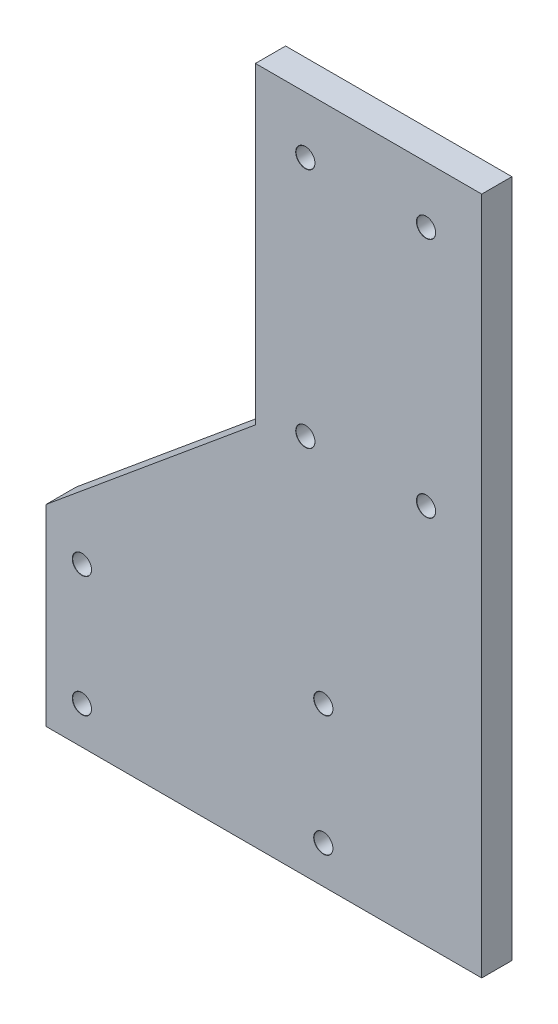
SolidWorks part; units mm, degrees
ref_plane "前视基准面" through (0, 0, 0) normal (0, 0, 1) x (1, 0, 0)
ref_plane "上视基准面" through (0, 0, 0) normal (0, 1, 0) x (1, 0, 0)
ref_plane "右视基准面" through (0, 0, 0) normal (1, 0, 0) x (0, 0, -1)
sketch "草图1" plane through (0, 0, 0) normal (0, 0, 1) x (1, 0, 0)
  line L0 (0, 0) -> (-41.5, 0)
  line L1 (-41.5, 0) -> (-41.5, 25.5)
  line L2 (-41.5, 25.5) -> (-13.75, 48.5)
  line L6 (14.05, -11.5) -> (-49.0563, -11.5) construction
  line L7 (-13.75, 48.5) -> (-13.75, 90)
  line L8 (-13.75, 90) -> (16.25, 90)
  line L9 (16.25, 90) -> (16.25, 0)
  line L10 (-92.1756, 35) -> (57.8057, 35) construction
  line L11 (-105.9645, 43.75) -> (59.2906, 43.75) construction
  line L12 (1.25, -9) -> (1.25, 87.7198) construction
  line L13 (0, 0) -> (16.25, 0)
  dimension "D1" = 41.5
  dimension "D2" = 90
  dimension "D3" = 25.5
  dimension "D4" = 30
  dimension "D5" = 41.5
  dimension "D6" = 35
  dimension "D7" = 8.75
extrude "凸台-拉伸1" add sketch "草图1" along normal blind 4
hole_wizard "Ø2.5mm 暗销孔1" positions "草图2" profile "草图3" hole size "Ø2.5" standard "ISO" end condition through all
sketch "草图2" plane through (0, 0, 4) normal (0, 0, 1) x (1, 0, 0)
  line L0 (-20.75, 0) -> (-20.75, 28.9161) construction
  line L1 (-41.5, 0) -> (16.25, 0) construction
  line L2 (-36.75, 21) -> (-4.75, 21) construction
  line L3 (1.25, 90) -> (1.25, 32.5659) construction
  line L6 (8.8664, 82.5) -> (-7.1336, 82.5) construction
  line L7 (-7.1336, 82.5) -> (-7.1336, 50.5) construction
  line L8 (-7.1336, 50.5) -> (8.8664, 50.5) construction
  line L9 (8.8664, 50.5) -> (8.8664, 82.5) construction
  point P6 (-36.75, 5)
  point P8 (-36.75, 21)
  point P12 (-4.75, 5)
  point P13 (-4.75, 21)
  point P44 (-7.1336, 82.5)
  point P47 (8.8664, 82.5)
  point P51 (-7.1336, 50.5)
  point P54 (8.8664, 50.5)
  dimension "D1" = 16
  dimension "D2" = 16
  dimension "D3" = 0
  dimension "D4" = 5
sketch "草图3" plane through (8.8664, 50.5, 4) normal (1, 0, 0) x (0, -1, 0)
  line L0 (0, 0) -> (0, 4)
  line L1 (0, 4) -> (1.25, 4)
  line L2 (1.25, 4) -> (1.25, 0.025)
  line L3 (1.25, 0.025) -> (1.275, 0)
  line L5 (1.275, 0) -> (0, 0)
  line L6 (-1.25, 0.025) -> (-1.275, 0) construction
  line L11 (0, -6.35) -> (0, 107.95) construction
  dimension "通孔孔直径" = 2.5
  dimension "通孔孔深度" = 4
  dimension "近端锥形沉头孔直径" = 2.55
  dimension "近端锥形沉头孔角度" = 90
